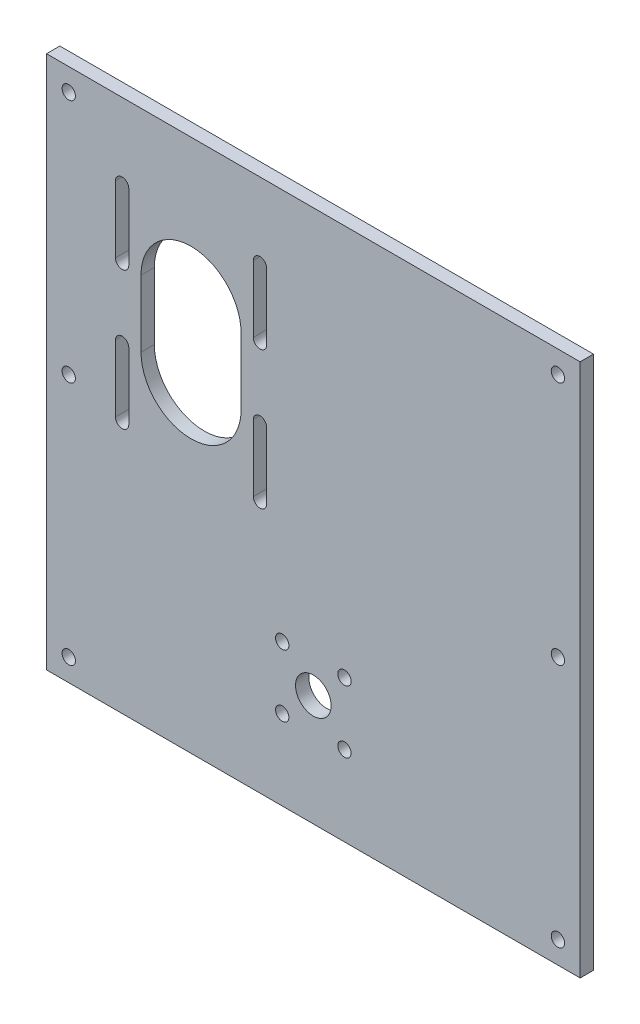
SolidWorks part; units mm, degrees
ref_plane "Plan de face" through (0, 0, 0) normal (0, 0, 1) x (1, 0, 0)
ref_plane "Plan de dessus" through (0, 0, 0) normal (0, 1, 0) x (1, 0, 0)
ref_plane "Plan de droite" through (0, 0, 0) normal (1, 0, 0) x (0, 0, -1)
sketch "Esquisse1" plane through (0, 0, 0) normal (0, 0, 1) x (1, 0, 0)
  line L0 (-27.5, 17.5) -> (-27.5, 32.5) construction
  line L1 (60, -65) -> (-60, -65)
  line L2 (60, -65) -> (60, 65)
  line L3 (60, 65) -> (-60, 65)
  line L4 (-60, -65) -> (-60, 65)
  line L5 (60, -65) -> (-60, 65) construction
  line L6 (60, 65) -> (-60, -65) construction
  line L9 (60, -55) -> (50, -55)
  line L10 (50, -65) -> (50, -55)
  line L13 (-60, -55) -> (-50, -55)
  line L14 (-50, -65) -> (-50, -55)
  line L15 (-38.75, 17.5) -> (-38.75, 32.5)
  line L16 (-16.25, 17.5) -> (-16.25, 32.5)
  line L17 (-43, 33) -> (-43, 48) construction
  line L18 (-44.5, 33) -> (-44.5, 48)
  line L19 (-41.5, 33) -> (-41.5, 48)
  line L20 (-43, 2) -> (-43, 17) construction
  line L21 (-44.5, 2) -> (-44.5, 17)
  line L22 (-41.5, 2) -> (-41.5, 17)
  line L23 (-27.5, 65) -> (-27.5, -65) construction
  line L24 (-27.5, 43.75) -> (-27.5, 6.25) construction
  line L27 (-12, 2) -> (-12, 17) construction
  line L30 (-10.5, 2) -> (-10.5, 17)
  line L31 (-13.5, 2) -> (-13.5, 17)
  line L32 (-12, 33) -> (-12, 48) construction
  line L33 (-10.5, 33) -> (-10.5, 48)
  line L34 (-13.5, 33) -> (-13.5, 48)
  arc A0 (-38.75, 17.5) -> (-16.25, 17.5) centre (-27.5, 17.5) ccw
  arc A1 (-16.25, 32.5) -> (-38.75, 32.5) centre (-27.5, 32.5) ccw
  arc A2 (-44.5, 33) -> (-41.5, 33) centre (-43, 33) ccw
  arc A3 (-41.5, 48) -> (-44.5, 48) centre (-43, 48) ccw
  arc A4 (-44.5, 2) -> (-41.5, 2) centre (-43, 2) ccw
  arc A5 (-41.5, 17) -> (-44.5, 17) centre (-43, 17) ccw
  arc A10 (-10.5, 2) -> (-13.5, 2) centre (-12, 2) cw
  arc A11 (-13.5, 17) -> (-10.5, 17) centre (-12, 17) cw
  arc A12 (-10.5, 33) -> (-13.5, 33) centre (-12, 33) cw
  arc A13 (-13.5, 48) -> (-10.5, 48) centre (-12, 48) cw
  point P0 (0, 0)
  point P14 (-27.5, 25)
  point P21 (-43, 40.5)
  point P28 (-43, 9.5)
  point P37 (-12, 9.5)
  point P44 (-12, 40.5)
  dimension "D13" = 90
  dimension "D1" = 10
  dimension "D2" = 10
  dimension "D3" = 130
  dimension "D4" = 120
  dimension "D5" = 32.5
  dimension "D6" = 15.5
  dimension "D7" = 22.5
  dimension "D8" = 3
  dimension "D9" = 15.5
  dimension "D10" = 15
  dimension "D11" = 3
  dimension "D12" = 31
extrude "Boss.-Extru.1" add sketch "Esquisse1" along normal blind 3 contours L14 L1 L10 L9 L2 L3 L4 L13 A5 L22 A4 L21 A3 L19 A2 L18 A1 L16 A0 L15 L31 A11 L30 A10 L34 A13 L33 A12 region at (1.7945, -0.8013, 0)
sketch "Esquisse2" plane through (0, 0, 3) normal (0, 0, 1) x (1, 0, 0)
  line L0 (-55, 65) -> (-55, -55) construction
  line L1 (60, 65) -> (-60, 65) construction
  line L2 (60, -55) -> (50, -55) construction
  line L3 (50, -60) -> (-50, -60) construction
  line L4 (50, -65) -> (50, -55) construction
  line L5 (-50, -65) -> (-50, -55) construction
  line L6 (0, 65) -> (0, -65) construction
  line L7 (50, -65) -> (-50, -65) construction
  circle A0 centre (45, -60) radius 1.5
  circle A3 centre (-55, -50) radius 1.5
  circle A4 centre (-55, 5) radius 1.5
  circle A5 centre (-55, 60) radius 1.5
  circle A9 centre (22.5, -60) radius 1.5
  circle A10 centre (0, -60) radius 1.5
  circle A11 centre (-22.5, -60) radius 1.5
  circle A12 centre (-45, -60) radius 1.5
  circle A13 centre (55, -50) radius 1.5
  circle A14 centre (55, 5) radius 1.5
  circle A15 centre (55, 60) radius 1.5
  dimension "D2" = 3
  dimension "D6" = 3
  dimension "D1" = 5
  dimension "D3" = 5
  dimension "D5" = 5
  dimension "D7" = 5
  dimension "D4" = 5
  dimension "D8" = 3
extrude "Enlèv. mat.-Extru.2" cut sketch "Esquisse2" against normal blind 3
sketch "Esquisse3" plane through (0, 0, 3) normal (0, 0, 1) x (1, 0, 0)
  line L3 (50, -65) -> (-50, -65) construction
  line L4 (0, 65) -> (0, -65) construction
  line L5 (60, 65) -> (-60, 65) construction
  line L6 (-7, -23) -> (7, -23) construction
  line L7 (7, -42) -> (-7, -42) construction
  line L8 (12, -37) -> (12, -23) construction
  line L9 (7, -18) -> (-7, -18) construction
  line L10 (-12, -37) -> (-12, -23) construction
  line L11 (12, -42) -> (-12, -18) construction
  line L12 (12, -18) -> (-12, -42) construction
  line L13 (-7, -23) -> (-7, -37) construction
  circle A0 centre (0, -30) radius 4
  arc A2 (-7, -42) -> (-12, -37) centre (-7, -37) cw construction
  arc A3 (7, -42) -> (12, -37) centre (7, -37) ccw construction
  arc A4 (12, -23) -> (7, -18) centre (7, -23) ccw construction
  arc A5 (-7, -18) -> (-12, -23) centre (-7, -23) ccw construction
  circle A6 centre (-7, -23) radius 1.5
  circle A7 centre (7, -23) radius 1.5
  circle A8 centre (7, -37) radius 1.5
  circle A9 centre (-7, -37) radius 1.5
  dimension "D1" = 8
  dimension "D2" = 35
  dimension "D3" = 14
  dimension "D4" = 5
  dimension "D5" = 3
  dimension "D8" = 14
  dimension "D6" = 2
  dimension "D7" = 2
extrude "Enlèv. mat.-Extru.3" cut sketch "Esquisse3" against normal blind 10
sketch "Esquisse4" plane through (0, 0, 3) normal (0, 0, 1) x (1, 0, 0)
  line L0 (-50, -55) -> (50, -55)
  line L1 (50, -55) -> (50, -76.4572)
  line L2 (50, -76.4572) -> (-50, -76.4572)
  line L3 (-50, -76.4572) -> (-50, -55)
extrude "Enlèv. mat.-Extru.4" cut sketch "Esquisse4" against normal blind 10
